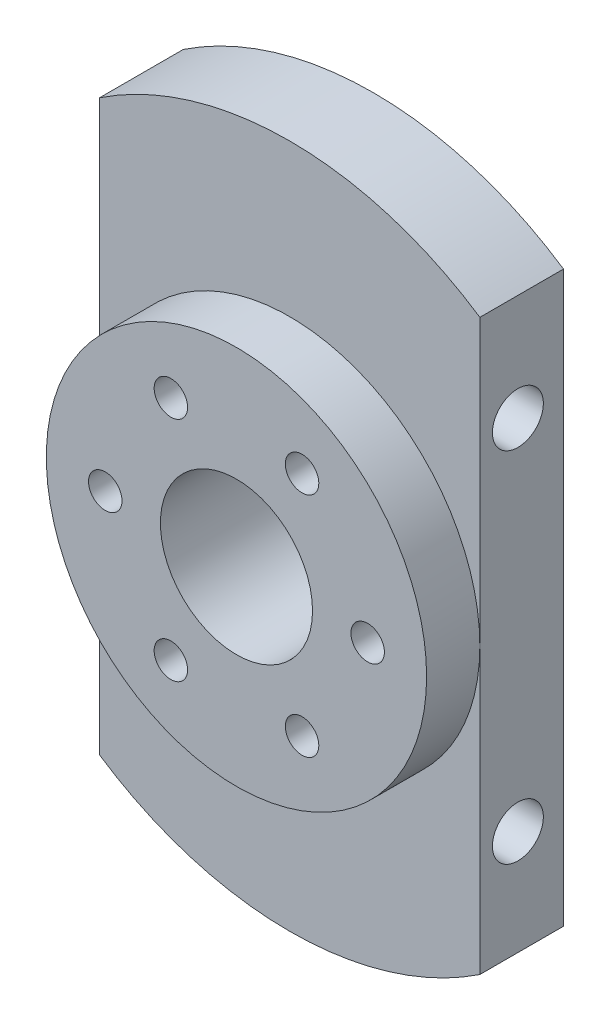
SolidWorks part; units mm, degrees
ref_plane "前视基准面" through (0, 0, 0) normal (0, 0, 1) x (1, 0, 0)
ref_plane "上视基准面" through (0, 0, 0) normal (0, 1, 0) x (1, 0, 0)
ref_plane "右视基准面" through (0, 0, 0) normal (1, 0, 0) x (0, 0, -1)
sketch "草图1" plane through (0, 0, 0) normal (0, 0, 1) x (1, 0, 0)
  circle A0 centre (0, 0) radius 45
  dimension "D1" = 90
extrude "凸台-拉伸1" add sketch "草图1" along normal blind 15
sketch "草图6" plane through (0, 0, 15) normal (0, 0, 1) x (1, 0, 0)
  circle A0 centre (0, 0) radius 10
extrude "切除-拉伸5" cut sketch "草图6" against normal blind 26
sketch "草图7" plane through (0, 0, 15) normal (0, 0, 1) x (1, 0, 0)
  circle A0 centre (17.25, 0) radius 2.2
  circle A1 centre (8.625, -14.9389) radius 2.2
  circle A2 centre (-8.625, -14.9389) radius 2.2
  circle A3 centre (-17.25, 0) radius 2.2
  circle A4 centre (-8.625, 14.9389) radius 2.2
  circle A5 centre (8.625, 14.9389) radius 2.2
  point P15 (0, 0)
  dimension "D1" = 4.4
  dimension "D2" = 17.25
  dimension "D3" = 6
extrude "切除-拉伸6" cut sketch "草图7" against normal through all
sketch "草图8" plane through (0, 0, 15) normal (0, 0, 1) x (1, 0, 0)
  line L0 (-45, 0) -> (45, 0) construction
  line L1 (-25, -37.4166) -> (-25, 37.4166)
  line L2 (0, 45) -> (0, -45) construction
  line L3 (25, -37.4166) -> (25, 37.4166)
  circle A0 centre (17.25, 0) radius 2.2 construction
  circle A1 centre (0, 0) radius 45
  circle A2 centre (0, 0) radius 45
  circle A3 centre (-17.25, 0) radius 2.2 construction
  circle A4 centre (17.25, 0) radius 2.2
  circle A5 centre (-17.25, 0) radius 2.2
  circle M11 centre (0, 0) radius 45
  dimension "D2" = 25
  dimension "D1" = 0
extrude "切除-拉伸7" cut sketch "草图8" against normal through all contours L1 M11 | L3 M11 region at (-33.1751, 0, 15) region at (33.1751, 0, 15)
sketch "草图9" plane through (25, 0, 0) normal (1, 0, 0) x (0, 0, -1)
  line L0 (-15, 0) -> (0, 0) construction
  line L5 (-15, 37.4166) -> (-15, -37.4166)
  line L6 (-15, -37.4166) -> (0, -37.4166)
  line L7 (0, -37.4166) -> (0, 37.4166)
  line L8 (0, 37.4166) -> (-15, 37.4166)
  line L9 (-15, 37.4166) -> (-15, -37.4166)
  line L10 (-15, -37.4166) -> (0, -37.4166)
  line L11 (0, -37.4166) -> (0, 37.4166)
  line L12 (0, 37.4166) -> (-15, 37.4166)
  circle A0 centre (-6, 23.45) radius 3.35
  circle A1 centre (-6, -23.63) radius 3.35
  dimension "D2" = 6.7
  dimension "D3" = 6.7
  dimension "D4" = 6
  dimension "D5" = 47.08
  dimension "D6" = 6
  dimension "D7" = 23.45
  dimension "D1" = 0
extrude "切除-拉伸8" cut sketch "草图9" against normal through all contours A0 | A1
sketch "草图11" plane through (0, 0, 0) normal (0, 0, -1) x (-1, 0, 0)
  circle A0 centre (-8.625, 14.9389) radius 4
  circle A1 centre (0, 0) radius 10
  circle A2 centre (0, 0) radius 10
  circle A3 centre (-8.625, -14.9389) radius 2.2
  circle A4 centre (-8.625, -14.9389) radius 2.2
  circle A5 centre (8.625, -14.9389) radius 2.2
  circle A6 centre (8.625, -14.9389) radius 2.2
  circle A7 centre (17.25, 0) radius 2.2
  circle A8 centre (17.25, 0) radius 2.2
  circle A9 centre (8.625, 14.9389) radius 2.2
  circle A10 centre (8.625, 14.9389) radius 2.2
  circle A11 centre (-8.625, 14.9389) radius 2.2
  circle A12 centre (-8.625, 14.9389) radius 2.2
  circle A13 centre (-17.25, 0) radius 2.2
  circle A14 centre (-17.25, 0) radius 2.2
  circle A15 centre (-17.25, 0) radius 4
  circle A16 centre (-8.625, -14.9389) radius 4
  circle A17 centre (8.625, 14.9389) radius 4
  circle A18 centre (8.625, -14.9389) radius 4
  circle A19 centre (17.25, 0) radius 4
  dimension "D8" = 8
  dimension "D9" = 8
  dimension "D10" = 8
  dimension "D11" = 8
  dimension "D12" = 8
  dimension "D13" = 8
  dimension "D1" = 0
  dimension "D2" = 0
  dimension "D3" = 0
  dimension "D4" = 0
  dimension "D5" = 0
  dimension "D6" = 0
  dimension "D7" = 0
extrude "切除-拉伸9" cut sketch "草图11" against normal blind 9 contours A15 | A0 | A16 | A18 | A19 | A17
sketch "草图12" plane through (25, 0, 0) normal (1, 0, 0) x (0, 0, -1)
  line L0 (0, -37.4166) -> (0, 37.4166) construction
  line L1 (0, -37.4166) -> (0, 37.4166)
  line L2 (0, -37.4166) -> (-15, -37.4166) construction
  line L3 (-15, -37.4166) -> (-15, 37.4166) construction
  line L4 (0, 37.4166) -> (-15, 37.4166) construction
  line L5 (0, -37.4166) -> (-15, -37.4166)
  line L6 (-15, -37.4166) -> (-15, 37.4166)
  line L7 (0, 37.4166) -> (-15, 37.4166)
  circle A1 centre (-6, -23.63) radius 3.35
  circle A2 centre (-6, -23.63) radius 3.35
  circle A3 centre (-6, 23.45) radius 3.35
  circle A4 centre (-6, 23.45) radius 3.35
  dimension "D1" = 0
  dimension "D2" = 0
sketch "草图13" plane through (0, 0, 15) normal (0, 0, 1) x (1, 0, 0)
  line L3 (-25, 37.4166) -> (-25, -37.4166)
  line L4 (25, -37.4166) -> (25, 37.4166)
  line L5 (-25, 37.4166) -> (-25, -37.4166)
  line L6 (25, -37.4166) -> (25, 37.4166)
  circle A0 centre (0, 0) radius 25
  arc A3 (-25, -37.4166) -> (25, -37.4166) centre (0, 0) ccw
  arc A4 (25, 37.4166) -> (-25, 37.4166) centre (0, 0) ccw
  arc A5 (-25, -37.4166) -> (25, -37.4166) centre (0, 0) ccw
  arc A6 (25, 37.4166) -> (-25, 37.4166) centre (0, 0) ccw
  line M6 (-25, 37.4166) -> (-25, -37.4166)
  arc M7 (-25, -37.4166) -> (25, -37.4166) centre (0, 0) ccw
  line M8 (25, -37.4166) -> (25, 37.4166)
  arc M9 (25, 37.4166) -> (-25, 37.4166) centre (0, 0) ccw
  dimension "D1" = 50
  dimension "D2" = 0
extrude "切除-拉伸10" cut sketch "草图13" against normal blind 4 contours A0 L6 M9 M6 | A0 L5 M7 M8 region at (0, 30.5289, 15) region at (0, -30.5289, 15)
sketch "草图14" plane through (0, 0, 15) normal (0, 0, 1) x (1, 0, 0)
  circle A0 centre (8.625, 14.9389) radius 2.2 construction
  circle A1 centre (0, 0) radius 25
  circle A2 centre (0, 0) radius 25
  circle A3 centre (17.25, 0) radius 2.2 construction
  circle A4 centre (0, 0) radius 10 construction
  circle A5 centre (8.625, -14.9389) radius 2.2 construction
  circle A6 centre (-8.625, -14.9389) radius 2.2 construction
  circle A7 centre (-17.25, 0) radius 2.2 construction
  circle A8 centre (-8.625, 14.9389) radius 2.2 construction
  circle A9 centre (8.625, 14.9389) radius 2.2
  circle A10 centre (17.25, 0) radius 2.2
  circle A11 centre (0, 0) radius 10
  circle A12 centre (8.625, -14.9389) radius 2.2
  circle A13 centre (-8.625, -14.9389) radius 2.2
  circle A14 centre (-17.25, 0) radius 2.2
  circle A15 centre (-8.625, 14.9389) radius 2.2
  dimension "D1" = 0
extrude "凸台-拉伸2" add sketch "草图14" along normal blind 3
move or copy body "实体-移动/复制1" [suppressed] bodies to move or copy 116 parameters "D1"=0, "D2"=0, "D3"=0
move or copy body "实体-移动/复制2" [suppressed] bodies to move or copy 117 parameters "D1"=0, "D2"=0, "D3"=0
move or copy body "实体-移动/复制3" [suppressed] bodies to move or copy 118 parameters "D1"=0, "D2"=0, "D3"=0
move or copy body "实体-移动/复制4" [suppressed] bodies to move or copy 119 parameters "D1"=0, "D2"=0, "D3"=0
